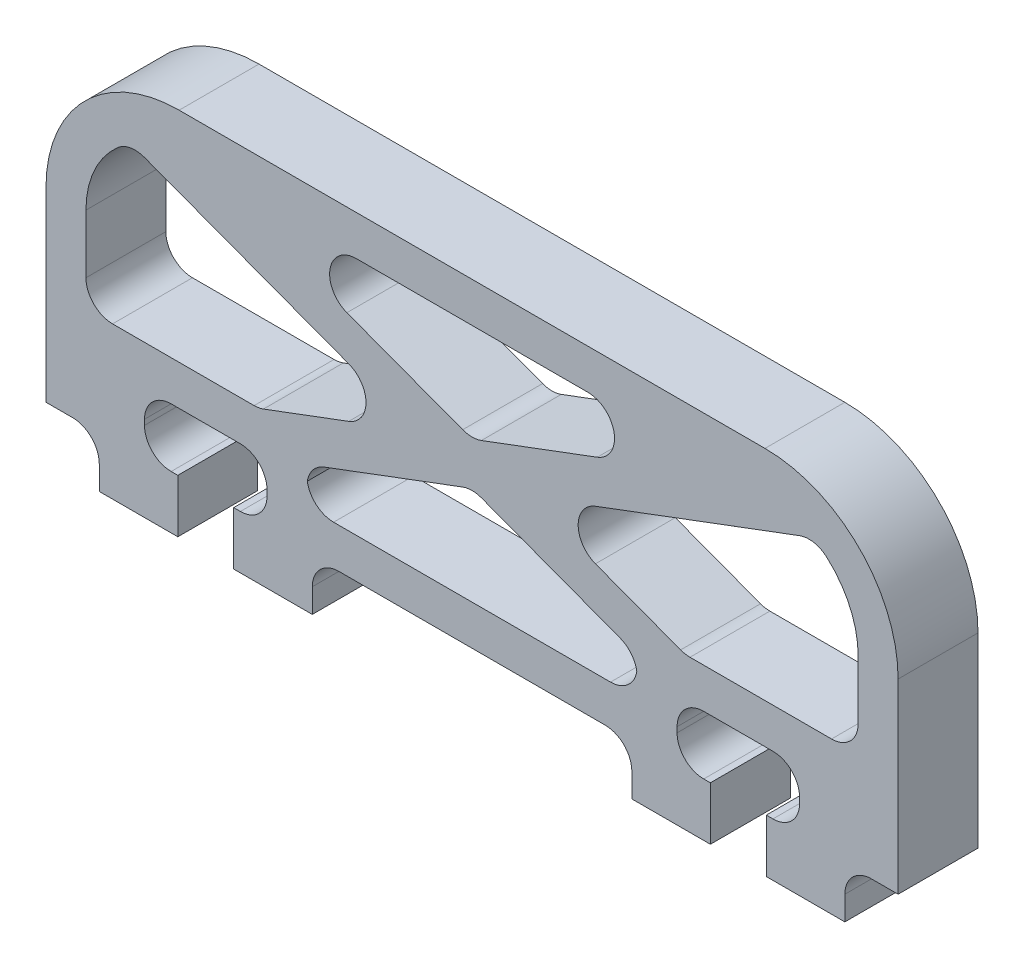
SolidWorks part; units mm, degrees
ref_plane "Front Plane" through (0, 0, 0) normal (0, 0, 1) x (1, 0, 0)
ref_plane "Top Plane" through (0, 0, 0) normal (0, 1, 0) x (1, 0, 0)
ref_plane "Right Plane" through (0, 0, 0) normal (1, 0, 0) x (0, 0, -1)
sketch "Sketch1" plane through (0, 0, 0) normal (0, 0, 1) x (1, 0, 0)
  line L0 (-10, -7.9) -> (-10, 6) construction
  line L1 (-16, 6) -> (16, 6)
  line L2 (-16, 6) -> (-16, -6)
  line L3 (-16, -6) -> (16, -6)
  line L4 (16, 6) -> (16, -6)
  line L5 (-16, 6) -> (16, -6) construction
  line L6 (-16, -6) -> (16, 6) construction
  line L7 (-16, -6) -> (-6, -6)
  line L9 (-14, -7.9) -> (-6, -7.9)
  line L10 (-6, -6) -> (-6, -7.9)
  line L11 (0, 6) -> (0, -6) construction
  line L12 (-11.05, -5.9) -> (-8.95, -5.9)
  line L13 (-11.05, -5.9) -> (-11.05, -7.9)
  line L14 (-11.05, -7.9) -> (-8.95, -7.9)
  line L15 (-8.95, -5.9) -> (-8.95, -7.9)
  line L16 (-11.05, -5.9) -> (-8.95, -7.9) construction
  line L17 (-11.05, -7.9) -> (-8.95, -5.9) construction
  line L18 (-12.3, -3.7) -> (-7.7, -3.7)
  line L19 (-12.3, -3.7) -> (-12.3, -5.9)
  line L20 (-12.3, -5.9) -> (-7.7, -5.9)
  line L21 (-7.7, -3.7) -> (-7.7, -5.9)
  line L22 (-12.3, -3.7) -> (-7.7, -5.9) construction
  line L23 (-12.3, -5.9) -> (-7.7, -3.7) construction
  line L24 (12.3, -3.7) -> (7.7, -3.7)
  line L25 (12.3, -3.7) -> (12.3, -5.9)
  line L26 (12.3, -5.9) -> (7.7, -5.9)
  line L27 (7.7, -3.7) -> (7.7, -5.9)
  line L28 (11.05, -5.9) -> (8.95, -5.9)
  line L29 (11.05, -5.9) -> (11.05, -7.9)
  line L30 (11.05, -7.9) -> (8.95, -7.9)
  line L31 (8.95, -5.9) -> (8.95, -7.9)
  line L32 (16, -6) -> (6, -6)
  line L33 (6, -6) -> (6, -7.9)
  line L34 (14, -7.9) -> (6, -7.9)
  line L36 (-14, -7.9) -> (-14, -6)
  line L37 (14, -7.9) -> (14, -6)
  point P0 (0, 0)
  point P11 (-10, -6.9)
  point P16 (-10, -4.8)
  dimension "D1" = 32
  dimension "D2" = 12
  dimension "D3" = 1.9
  dimension "D4" = 8
  dimension "D5" = 2.1
  dimension "D6" = 2
  dimension "D7" = 2.2
  dimension "D8" = 4.6
  dimension "D9" = 2
extrude "Boss-Extrude2" add sketch "Sketch1" along normal blind 3 contours L31 L26 L27 L24 L25 L29 L3 L4 L1 L2 L13 L20 L19 L18 L21 L15 | L3 L15 L9 L10 | L13 L3 L9 | L34 L31 L3 L33 | L3 L29 L34 region at (0, 0.2743, 0) region at (-12.525, -6.95, 0) region at (12.525, -6.95, 0) region at (-7.475, -6.95, 0) region at (7.475, -6.95, 0)
fillet "Fillet1" radius 5 2 edges at (16, 6, 1.5) (-16, 6, 1.5)
sketch "Sketch2" plane through (0, 0, 3) normal (0, 0, 1) x (1, 0, 0)
  line L0 (-6, -6) -> (6, -6) construction
  line L1 (16, -6) -> (-16, -6)
  line L2 (16, -6) -> (16, 6)
  line L3 (16, 6) -> (-16, 6)
  line L4 (-16, -6) -> (-16, 6)
  line L5 (16, -6) -> (-16, 6) construction
  line L6 (16, 6) -> (-16, -6) construction
  line L8 (16.2633, -5.2978) -> (-15.7367, 6.7022)
  line L9 (15.7367, 6.7022) -> (-16.2633, -5.2978)
  line L10 (15.7367, -6.7022) -> (-16.2633, 5.2978)
  line L11 (16.2633, 5.2978) -> (-15.7367, -6.7022)
  line L36 (-16, 1) -> (-16, -6) construction
  line L37 (-13.8, -2.2) -> (-14.5, -2.2)
  line L38 (13.8, -2.2) -> (14.5, -2.2)
  line L60 (11, 4.5) -> (-11, 4.5)
  line L61 (14.5, -4.5) -> (14.5, 1)
  line L62 (-13.8, -2.2) -> (-6.2, -2.2)
  line L63 (-6.2, -2.2) -> (-6.2, -4.5)
  line L64 (-6.2, -4.5) -> (6.2, -4.5)
  line L65 (6.2, -4.5) -> (6.2, -2.2)
  line L66 (6.2, -2.2) -> (13.8, -2.2)
  line L67 (14.5, -4.5) -> (14.5, 1)
  line L68 (11, 4.5) -> (-11, 4.5)
  line L70 (-13.8, -2.2) -> (-6.2, -2.2)
  line L71 (-6.2, -2.2) -> (-6.2, -4.5)
  line L72 (-6.2, -4.5) -> (6.2, -4.5)
  line L73 (6.2, -4.5) -> (6.2, -2.2)
  line L74 (6.2, -2.2) -> (13.8, -2.2)
  line L80 (-14.5, 1) -> (-14.5, -4.5)
  line L81 (-14.5, 1) -> (-14.5, -4.5)
  line L83 (-13.8, -4.5) -> (-13.8, -2.2)
  line L84 (-13.8, -4.5) -> (-13.8, -2.2)
  line L85 (13.8, -2.2) -> (13.8, -4.5)
  line L86 (13.8, -2.2) -> (13.8, -4.5)
  line L87 (13.8, -4.5) -> (14.5, -4.5)
  line L88 (13.8, -4.5) -> (14.5, -4.5)
  line L89 (-14.5, -4.5) -> (-13.8, -4.5)
  line L90 (-14.5, -4.5) -> (-13.8, -4.5)
  arc A4 (14.5, 1) -> (11, 4.5) centre (11, 1) ccw
  arc A5 (14.5, 1) -> (11, 4.5) centre (11, 1) ccw
  arc A8 (-11, 4.5) -> (-14.5, 1) centre (-11, 1) ccw
  arc A9 (-11, 4.5) -> (-14.5, 1) centre (-11, 1) ccw
  point P0 (0, 0)
  dimension "D1" = 0.75
  dimension "D2" = 0.75
  dimension "D3" = 1.5
extrude "Cut-Extrude1" cut sketch "Sketch2" against normal up to next contours L10 A9 L81 L90 L9 L84 L70 | L9 L68 L8 | L67 A5 L11 L8 L74 L86 L88 | L72 L73 L10 L11 L71 region at (0, -3.143, 3) region at (9.8969, 0.3518, 3) region at (-9.8969, 0.3518, 3) region at (0, 3.267, 3)
fillet "Fillet2" radius 1 16 edges at (6.2, -4.5, 1.5) (6.2, -3.126, 1.5) (-6.2, -4.5, 1.5) (-6.2, -3.126, 1.5) (0, -0.801, 1.5) (8.0027, -2.2, 1.5) (2.136, 0, 1.5) (9.864, 4.5, 1.5) (-9.864, 4.5, 1.5) (0, 0.801, 1.5) (-2.136, 0, 1.5) (-8.0027, -2.2, 1.5) (14.5, -2.2, 1.5) (12.8027, 4, 1.5) (-12.8027, 4, 1.5) (-14.5, -2.2, 1.5)
fillet "Fillet3" radius 1 12 edges at (12.3, -5.9, 1.5) (12.3, -3.7, 1.5) (7.7, -3.7, 1.5) (7.7, -5.9, 1.5) (-12.3, -5.9, 1.5) (-7.7, -5.9, 1.5) (-7.7, -3.7, 1.5) (-12.3, -3.7, 1.5) (14, -6, 1.5) (6, -6, 1.5) (-14, -6, 1.5) (-6, -6, 1.5)
